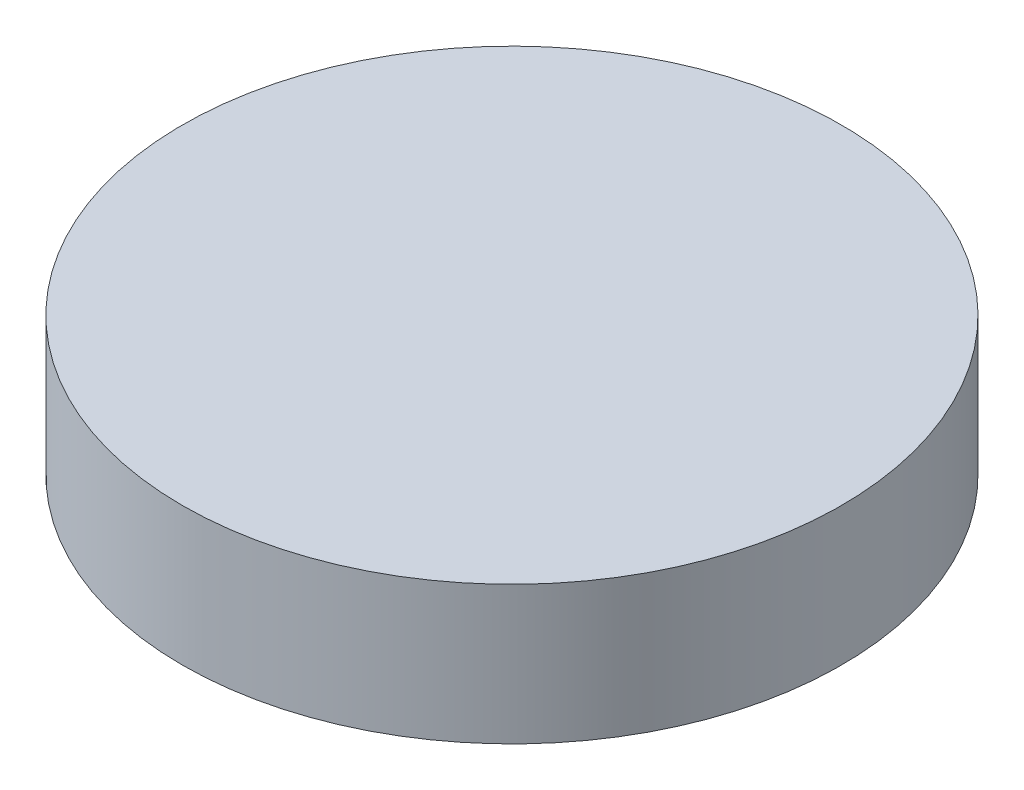
SolidWorks part; units mm, degrees
ref_plane "Ebene vorne" through (0, 0, 0) normal (0, 0, 1) x (1, 0, 0)
ref_plane "Ebene oben" through (0, 0, 0) normal (0, 1, 0) x (1, 0, 0)
ref_plane "Ebene rechts" through (0, 0, 0) normal (1, 0, 0) x (0, 0, -1)
sketch "Sketch1" plane through (0, 0, 0) normal (0, 1, 0) x (1, 0, 0)
  circle A0 centre (0, 0) radius 76.29
  dimension "D1" = 152.58
extrude "Boss-Extrude1" add sketch "Sketch1" along normal blind 32
